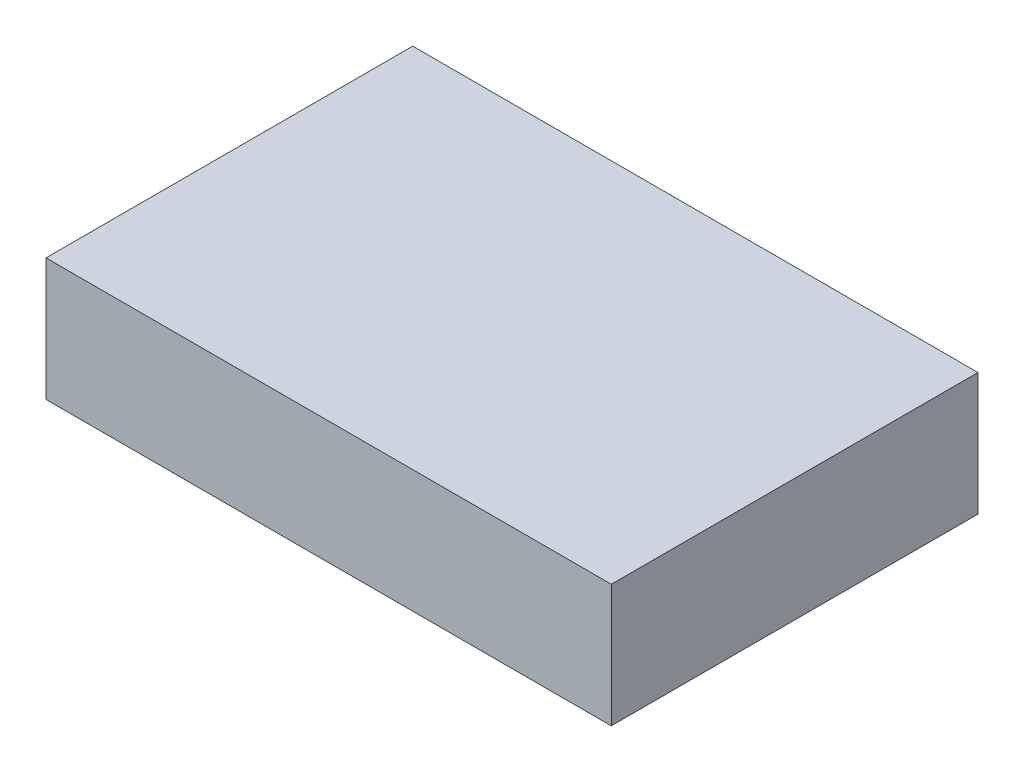
SolidWorks part; units mm, degrees
ref_plane "Front Plane" through (0, 0, 0) normal (0, 0, 1) x (1, 0, 0)
ref_plane "Top Plane" through (0, 0, 0) normal (0, 1, 0) x (1, 0, 0)
ref_plane "Right Plane" through (0, 0, 0) normal (1, 0, 0) x (0, 0, -1)
sketch "Sketch1" plane through (0, 0, 0) normal (0, 1, 0) x (1, 0, 0)
  line L1 (16.7, 343.2577) -> (631.38, 343.2577)
  line L2 (16.7, 343.2577) -> (16.7, -55.5223)
  line L3 (16.7, -55.5223) -> (631.38, -55.5223)
  line L4 (631.38, 343.2577) -> (631.38, -55.5223)
extrude "Boss-Extrude2" add sketch "Sketch1" along normal blind 133.35
